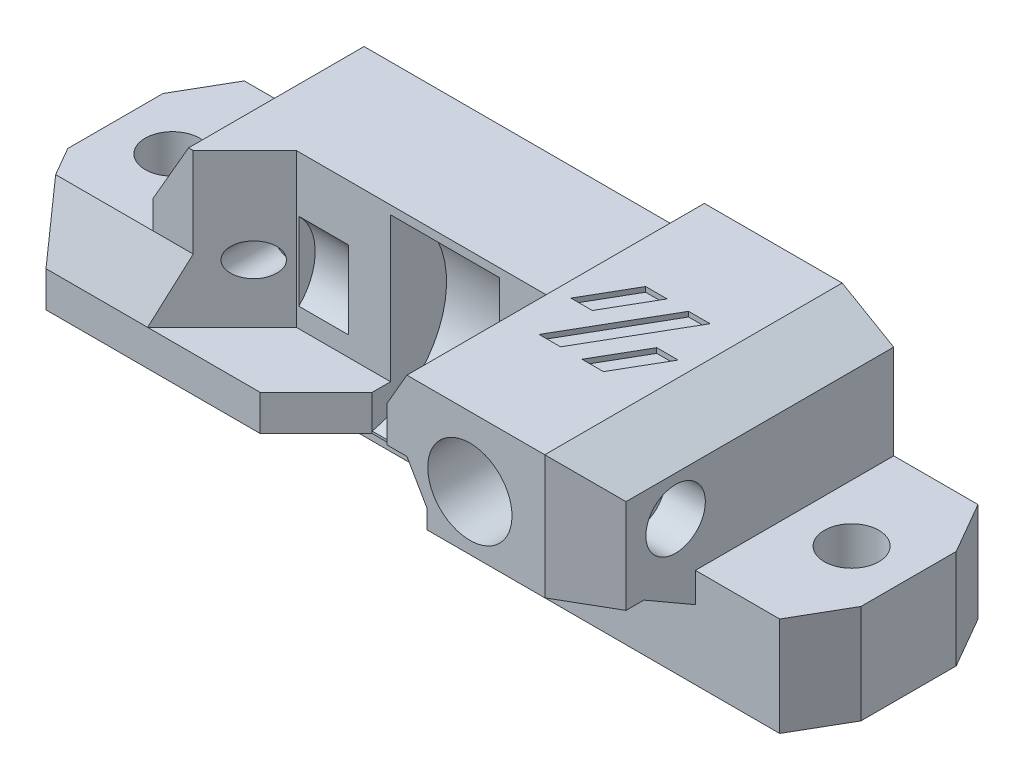
SolidWorks part; units mm, degrees
material "ABS"
ref_plane "Ebene vorne" through (0, 0, 0) normal (0, 0, 1) x (1, 0, 0)
ref_plane "Ebene oben" through (0, 0, 0) normal (0, 1, 0) x (1, 0, 0)
ref_plane "Ebene rechts" through (0, 0, 0) normal (1, 0, 0) x (0, 0, -1)
sketch "Skizze1" plane through (0, 0, 0) normal (1, 0, 0) x (0, 0, -1)
  line L0 (0, 0) -> (0, 20)
  line L1 (0, 0) -> (20, 0)
  line L2 (-19.5, -490) -> (-19.5, 10) construction
  line L3 (-19.5, 10) -> (-11.5, 10) construction
  line L4 (-11.5, 10) -> (-11.5, -490) construction
  line L5 (-11.5, -490) -> (-19.5, -490) construction
  line L6 (-15.5, 10) -> (-15.5, -490) construction
  line L7 (-9.5, -7) -> (-9.5, -10) construction
  line L8 (-22.5, 20) -> (-22.5, -10)
  line L9 (-22.5, -10) -> (20, -10)
  line L10 (20, -10) -> (20, 0)
  line L11 (0, 20) -> (-22.5, 20)
  line L12 (-23.5, -11) -> (-7.5, -11) construction
  line L13 (-7.5, -11) -> (-5.5, -16.495) construction
  line L14 (-5.5, -16.495) -> (-5.5, -78.505) construction
  line L15 (-5.5, -78.505) -> (-7.5, -84) construction
  line L16 (-7.5, -84) -> (-23.5, -84) construction
  line L17 (-23.5, -84) -> (-25.5, -78.505) construction
  line L18 (-25.5, -78.505) -> (-25.5, -16.495) construction
  line L19 (-25.5, -16.495) -> (-23.5, -11) construction
  line L20 (-2, 2.5) -> (-2, -84) construction
  circle A0 centre (-9.5, 2.5) radius 6.5 construction
  circle A1 centre (-9.5, 2.5) radius 7.5 construction
  circle A2 centre (-9.5, 2.5) radius 9.5 construction
  point P14 (-16, 2.5)
  point P15 (-9.5, -7)
  point P29 (-15.5, -11)
  point P30 (-2, 2.5)
  dimension "D2" = 15
  dimension "D3" = 13
  dimension "D5" = 19
  dimension "D1" = 20
  dimension "D4" = 15.5
  dimension "D6" = 500
  dimension "D7" = 10
  dimension "D8" = 8
  dimension "D9" = 0.5
  dimension "D10" = 3
  dimension "D11" = 10
  dimension "D12" = 17.5
  dimension "D13" = 3
  dimension "D14" = 73
  dimension "D15" = 70
  dimension "D16" = 70
  dimension "D17" = 2
  dimension "D18" = 20
  dimension "D19" = 1
  dimension "D20" = 3.5
extrude "Aufsatz-Linear austragen1" add sketch "Skizze1" along normal blind 80
sketch "Skizze2" plane through (0, 20, 0) normal (0, 1, 0) x (1, 0, 0)
  line L0 (80, 0) -> (80, -22.5) construction
  line L1 (80, 0) -> (0, 0) construction
  circle A0 centre (55.75, -15.5) radius 4.25
  point P2 (60, -15.5)
  dimension "D1" = 8.5
  dimension "D2" = 20
  dimension "D3" = 15.5
extrude "Schnitt-Linear austragen1" cut sketch "Skizze2" against normal up to surface (30 mm away) up to face at (40, -10, 1.25)
sketch "Skizze3" plane through (0, -10, 0) normal (0, -1, 0) x (1, 0, 0)
  line L0 (48.4, 9.5) -> (18.6, 9.5) construction
  line L1 (32.75, 16) -> (38.75, 16) construction
  line L2 (32.75, 16) -> (32.75, 3) construction
  line L3 (32.75, 3) -> (38.75, 3) construction
  line L4 (38.75, 16) -> (38.75, 3) construction
  line L5 (35.75, 16) -> (35.75, 3) construction
  line L6 (80, 0) -> (0, 0) construction
  line L7 (45.75, 12) -> (25.75, 12) construction
  line L8 (45.75, 12) -> (45.75, 7) construction
  line L9 (45.75, 7) -> (25.75, 7) construction
  line L10 (25.75, 12) -> (25.75, 7) construction
  line L11 (25.75, 14.25) -> (21.25, 14.25) construction
  line L12 (25.75, 14.25) -> (25.75, 4.75) construction
  line L13 (25.75, 4.75) -> (21.25, 4.75) construction
  line L14 (21.25, 14.25) -> (21.25, 4.75) construction
  line L15 (31.75, 17) -> (32.75, 17) construction
  line L16 (31.75, 17) -> (31.75, 2) construction
  line L17 (31.75, 2) -> (32.75, 2) construction
  line L18 (32.75, 17) -> (32.75, 2) construction
  line L19 (39.75, 17) -> (38.75, 17) construction
  line L20 (39.75, 17) -> (39.75, 2) construction
  line L21 (39.75, 2) -> (38.75, 2) construction
  line L22 (38.75, 17) -> (38.75, 2) construction
  line L23 (80, 0) -> (0, 0) construction
  line L24 (49.1736, 15) -> (17.8264, 15) construction
  line L25 (17.8264, 4) -> (49.1736, 4) construction
  line L26 (49.1736, 15) -> (51.05, 11.75) construction
  line L27 (51.05, 11.75) -> (51.05, 7.25) construction
  line L28 (51.05, 7.25) -> (49.1736, 4) construction
  line L29 (33.5, 15) -> (33.5, 4) construction
  line L30 (15.95, 7.25) -> (17.8264, 4) construction
  line L31 (15.95, 11.75) -> (15.95, 7.25) construction
  line L32 (17.8264, 15) -> (15.95, 11.75) construction
  line L33 (49.3991, 22.5) -> (47.4046, 19.0453)
  line L34 (80, 22.5) -> (0, 22.5) construction
  line L35 (47.4046, 19.0453) -> (47.4046, 15.4)
  line L36 (47.4046, 15.4) -> (49.4046, 15.4)
  line L37 (49.4046, 15.4) -> (51.45, 11.8572)
  line L38 (51.45, 11.8572) -> (51.45, 7.1428)
  line L39 (51.45, 7.1428) -> (49.4046, 3.6)
  line L40 (49.4046, 3.6) -> (17.5954, 3.6)
  line L41 (47.4046, 15.4) -> (47.4046, 15) construction
  line L42 (49.1736, 15) -> (49.52, 15.2) construction
  line L43 (51.05, 11.75) -> (51.45, 11.75) construction
  line L44 (51.05, 7.25) -> (51.3964, 7.05) construction
  line L45 (15.55, 11.8572) -> (17.5954, 15.4)
  line L46 (0, 22.5) -> (0, -20) construction
  line L47 (15.55, 11.8572) -> (15.55, 7.1428)
  line L48 (15.55, 7.1428) -> (17.5954, 3.6)
  line L49 (15.95, 11.75) -> (15.55, 11.75) construction
  line L50 (15.95, 7.25) -> (15.6036, 7.05) construction
  line L51 (17.8264, 4) -> (17.8264, 3.6) construction
  line L52 (17.8264, 0) -> (0, 0) construction
  line L53 (0, 0) -> (0, 19.0453) construction
  line L54 (17.5954, 15.4) -> (19.5954, 15.4)
  line L55 (19.5954, 19.0453) -> (0, 19.0453)
  line L56 (17.8264, 15) -> (17.48, 15.2) construction
  line L57 (17.8264, 15) -> (17.8264, 15.4) construction
  line L58 (19.5954, 15.4) -> (19.5954, 19.0453)
  line L59 (0, 19.0453) -> (0, 22.5)
  line L60 (0, 22.5) -> (49.3991, 22.5)
  line L63 (39.75, 14.25) -> (40.75, 14.25) construction
  line L64 (39.75, 14.25) -> (39.75, 4.75) construction
  line L65 (39.75, 4.75) -> (40.75, 4.75) construction
  line L66 (40.75, 14.25) -> (40.75, 4.75) construction
  line L67 (31.75, 14.25) -> (30.75, 14.25) construction
  line L68 (31.75, 14.25) -> (31.75, 4.75) construction
  line L69 (31.75, 4.75) -> (30.75, 4.75) construction
  line L70 (30.75, 14.25) -> (30.75, 4.75) construction
  circle A0 centre (48.4, 9.5) radius 1.65
  circle A1 centre (18.6, 9.5) radius 1.65
  circle A2 centre (55.75, 15.5) radius 4.25 construction
  circle A3 centre (55.75, 15.5) radius 4.25 construction
  point P8 (32.75, 9.5)
  point P11 (35.75, 9.5)
  point P22 (21.25, 9.5)
  point P23 (45.75, 9.5)
  point P26 (51.5, 15.5)
  point P27 (50.05, 9.5)
  point P28 (46.75, 9.5)
  point P37 (20.25, 9.5)
  point P44 (51.05, 9.5)
  point P51 (16.95, 9.5)
  point P91 (40.75, 9.5)
  dimension "D1" = 3.3
  dimension "D4" = 20
  dimension "D3" = 6
  dimension "D5" = 20
  dimension "D6" = 4.5
  dimension "D7" = 9.5
  dimension "D8" = 5
  dimension "D9" = 1
  dimension "D10" = 1.45
  dimension "D11" = 13
  dimension "D12" = 8
  dimension "D13" = 5
  dimension "D14" = 1
  dimension "D15" = 29.8
  dimension "D16" = 0.5
  dimension "D17" = 15
  dimension "D18" = 1
  dimension "D19" = 1
  dimension "D20" = 1
  dimension "D21" = 60
  dimension "D22" = 4.5
  dimension "D23" = 1
  dimension "D24" = 0.4
  dimension "D25" = 9
  dimension "D26" = 2
  dimension "D27" = 10
  dimension "D28" = 9.5
  dimension "D29" = 5
extrude "Schnitt-Linear austragen2" cut sketch "Skizze3" against normal offset from surface (17.5 mm away) 12.5 up to face at (55.75, 20, 19.75)
sketch "Skizze4" plane through (0, -10, 0) normal (0, -1, 0) x (1, 0, 0)
  circle A1 centre (18.6, 9.5) radius 1.65
  circle A2 centre (18.6, 9.5) radius 1.65
  circle A3 centre (48.4, 9.5) radius 1.65
  circle A4 centre (48.4, 9.5) radius 1.65
  dimension "D1" = 0
  dimension "D2" = 0
extrude "Schnitt-Linear austragen3" cut sketch "Skizze4" against normal up to surface (30 mm away) up to face at (55.75, 20, 19.75)
sketch "Skizze5" plane through (0, 0, 0) normal (0, 0, -1) x (-1, 0, 0)
  line L0 (-80, 0) -> (0, 0) construction
  line L1 (-80, 0) -> (-80, 20) construction
  line L2 (-5.75, 10) -> (0, 10) construction
  line L3 (0, 0) -> (0, 20) construction
  line L4 (-74.25, 10) -> (-80, 10) construction
  circle A0 centre (-5.75, 10) radius 2.75
  circle A1 centre (-74.25, 10) radius 2.75
  point P8 (-77, 10)
  point P13 (-3, 10)
  dimension "D2" = 5.5
  dimension "D1" = 10
  dimension "D3" = 3
extrude "Schnitt-Linear austragen4" cut sketch "Skizze5" against normal up to surface (22.5 mm away) up to face at (43.133, 5.8333, 22.5)
sketch "Skizze6" plane through (0, 0, 0) normal (0, 1, 0) x (1, 0, 0)
  line L0 (0, 10) -> (80, 10) construction
  line L2 (0, 20) -> (0, 0) construction
  line L3 (80, 20) -> (80, 0) construction
  line L4 (80, 0) -> (0, 0) construction
  circle A0 centre (40, 10) radius 2.75
  dimension "D2" = 5.5
  dimension "D1" = 10
extrude "Schnitt-Linear austragen5" cut sketch "Skizze6" against normal up to surface (10 mm away) up to face at (55.75, -10, 19.75)
sketch "Skizze7" plane through (0, 20, 0) normal (0, 1, 0) x (1, 0, 0)
  line L1 (21.8909, -9.5) -> (20.2454, -6.65)
  line L2 (20.2454, -6.65) -> (16.9546, -6.65)
  line L3 (16.9546, -6.65) -> (15.3091, -9.5)
  line L4 (15.3091, -9.5) -> (16.9546, -12.35)
  line L5 (16.9546, -12.35) -> (20.2454, -12.35)
  line L6 (20.2454, -12.35) -> (21.8909, -9.5)
  line L7 (51.6909, -9.5) -> (50.0454, -6.65)
  line L8 (50.0454, -6.65) -> (46.7546, -6.65)
  line L9 (46.7546, -6.65) -> (45.1091, -9.5)
  line L10 (45.1091, -9.5) -> (46.7546, -12.35)
  line L11 (46.7546, -12.35) -> (50.0454, -12.35)
  line L12 (50.0454, -12.35) -> (51.6909, -9.5)
  circle A0 centre (18.6, -9.5) radius 2.85 construction
  circle A1 centre (48.4, -9.5) radius 2.85 construction
  dimension "D1" = 5.7
extrude "Schnitt-Linear austragen6" cut sketch "Skizze7" against normal offset from surface (9.5 mm away) 3 up to face at (31.0127, 7.5, 13.9291)
sketch "Skizze8" plane through (0, 7.5, 0) normal (0, -1, 0) x (1, 0, 0)
  line L0 (49.3991, 22.5) -> (47.4046, 19.0453) construction
  line L2 (49.3991, 22.5) -> (47.4046, 19.0453)
  line L3 (0, 22.5) -> (0, 10)
  line L4 (0, 22.5) -> (49.3991, 22.5)
  line L5 (47.4046, 19.0453) -> (15.0812, 19.0453)
  line L6 (80, 22.5) -> (68.5, 22.5)
  line L7 (80, 22.5) -> (80, 10)
  line L8 (80, 10) -> (68.5, 10)
  line L9 (80, 0) -> (80, 22.5) construction
  line L10 (80, 22.5) -> (0, 22.5) construction
  line L12 (68.5, 22.5) -> (68.5, 10)
  line L13 (55.75, 15.5) -> (47.9558, 20) construction
  line L15 (71.5, 0) -> (77, 0) construction
  line L16 (71.5, 0) -> (77, 0) construction
  line L17 (19.5954, 19.0453) -> (6.8956, 19.0453) construction
  line L18 (0, 10) -> (11.5, 10)
  line L19 (11.5, 10) -> (11.5, 12.8424)
  line L20 (11.5, 12.8424) -> (15.0812, 19.0453)
  line L21 (3, 0) -> (8.5, 0) construction
  line L22 (3, 0) -> (8.5, 0) construction
  line L24 (15.55, 11.8572) -> (17.5954, 15.4) construction
  circle A0 centre (55.75, 15.5) radius 4.25 construction
  circle A1 centre (55.75, 15.5) radius 4.25 construction
  point P15 (60, 15.5)
  dimension "D2" = 10
  dimension "D3" = 3
  dimension "D4" = 3
  dimension "D5" = 4
extrude "Schnitt-Linear austragen7" cut sketch "Skizze8" against normal up to surface and the other way up to surface up to face at (48.4, 20, 9.5) other way up to face at (40, -10, -7.25)
sketch "Skizze9" plane through (51.45, 0, 0) normal (-1, 0, 0) x (0, 0, 1)
  line L0 (9.5, 7.5) -> (9.5, -10) construction
  line L1 (11.8572, 7.5) -> (7.1428, 7.5) construction
  line L2 (7.1428, -10) -> (11.8572, -10) construction
  line L3 (0, 3.65) -> (0, -10)
  line L4 (0, -10) -> (19, -10)
  line L5 (19, -10) -> (19, 3.65)
  circle A0 centre (9.5, 3.65) radius 6.5 construction
  circle A1 centre (9.5, 3.65) radius 9.5 construction
  arc A2 (19, 3.65) -> (0, 3.65) centre (9.5, 3.65) ccw
  line M1 (11.8572, 7.5) -> (7.1428, 7.5)
  line M2 (7.1428, 7.5) -> (7.1428, -10)
  line M3 (7.1428, -10) -> (11.8572, -10)
  line M4 (11.8572, -10) -> (11.8572, 7.5)
  dimension "D1" = 13
  dimension "D2" = 19
  dimension "D3" = 3.85
extrude "Schnitt-Linear austragen8" cut sketch "Skizze9" along normal blind 11 from offset 10.2 contours L5 A2 L3 L4 M2 M1 M4 | M4 M1 M2 M3
sketch "Skizze10" plane through (51.45, 0, 0) normal (-1, 0, 0) x (0, 0, 1)
  line L0 (9.5, 7.5) -> (9.5, 3.65) construction
  line L1 (11.8572, 7.5) -> (7.1428, 7.5) construction
  circle A0 centre (9.5, 3.65) radius 5.5
  dimension "D1" = 11
  dimension "D2" = 3.85
extrude "Schnitt-Linear austragen9" cut sketch "Skizze10" along normal blind 5 from offset 25.45
sketch "Skizze11" plane through (0, 0, 0) normal (0, 0, -1) x (-1, 0, 0)
  line L0 (-20.75, 7.5) -> (-15.55, 2.3)
  line L1 (-46.25, 7.5) -> (-51.45, 7.5)
  line L4 (-15.55, 2.3) -> (-15.55, 7.5)
  line L6 (-15.55, 7.5) -> (-20.75, 7.5)
  line L8 (-15.55, 7.5) -> (-15.55, -10) construction
  line L9 (-16.95, 10.5) -> (-20.25, 10.5) construction
  line L10 (-16.95, 10.5) -> (-20.25, 10.5) construction
  line L11 (-46.75, 10.5) -> (-50.05, 10.5) construction
  line L12 (-16.95, 10.5) -> (-20.25, 10.5)
  line L13 (-46.75, 10.5) -> (-50.05, 10.5) construction
  line L14 (-18.6, 10.5) -> (-18.6, 7.5) construction
  line L15 (-48.4, 10.5) -> (-48.4, 7.5) construction
  line L16 (-51.45, 7.5) -> (-51.45, 2.3)
  line L17 (-51.45, 2.3) -> (-46.25, 7.5)
  line L21 (-51.45, 7.5) -> (-51.45, -10) construction
  line L22 (-19.5954, 7.5) -> (-47.4046, 7.5) construction
  dimension "D2" = 2.15
  dimension "D3" = 45
extrude "Aufsatz-Linear austragen2" add sketch "Skizze11" against normal up to surface (19.0453 mm away)
sketch "Skizze12" plane through (0, 10.5, 0) normal (0, 1, 0) x (1, 0, 0)
  circle A0 centre (18.6, -9.5) radius 1.65 construction
  circle A1 centre (48.4, -9.5) radius 1.65 construction
  circle A2 centre (18.6, -9.5) radius 1.65
  circle A3 centre (48.4, -9.5) radius 1.65
extrude "Schnitt-Linear austragen10" cut sketch "Skizze12" against normal up to surface (20.5 mm away) up to face at (40, -10, -7.25)
chamfer "Fase1" distance 1.6 angle 45 2 edges at (48.4, 10.5, 7.85) (18.6, 10.5, 7.85)
sketch "Skizze15" plane through (80, 0, 0) normal (1, 0, 0) x (0, 0, -1)
  line L1 (0, 0) -> (20, 0)
  line L2 (0, 0) -> (0, -10)
  line L3 (0, -10) -> (20, -10)
  line L4 (20, 0) -> (20, -10)
extrude "Schnitt-Linear austragen12" cut sketch "Skizze15" against normal up to surface (80 mm away) up to face at (0, 3.3333, -3.3333)
sketch "Skizze16" plane through (0, 0, 19.0453) normal (0, 0, 1) x (1, 0, 0)
  line L0 (0, -10) -> (0, 2.3)
  line L1 (0, 2.3) -> (15.55, 2.3)
  line L2 (15.55, 2.3) -> (19.5954, 6.3454)
  line L3 (19.5954, 6.3454) -> (19.5954, -10)
  line L4 (19.5954, -10) -> (0, -10)
  line L5 (0, 20) -> (0, -10) construction
  line L6 (11.5, -10) -> (0, -10) construction
extrude "Schnitt-Linear austragen13" cut sketch "Skizze16" against normal up to surface (15.4453 mm away) up to face at (45.5118, -0.1309, 3.6)
sketch "Skizze17" plane through (0, 0, 3.6) normal (0, 0, 1) x (1, 0, 0)
  line L0 (0, 2.3) -> (0, -10) construction
  line L1 (49.4046, -10) -> (0, -10)
  line L2 (49.4046, -10) -> (49.4046, 0)
  line L3 (49.4046, 0) -> (0, 0)
  line L4 (0, -10) -> (0, 0)
  line L5 (11.5, 20) -> (0, 20) construction
  dimension "D1" = 20
extrude "Schnitt-Linear austragen14" cut sketch "Skizze17" against normal up to surface (3.6 mm away) up to face at (71.5, 10, 0)
sketch "Skizze20" plane through (0, 0, 0) normal (-1, 0, 0) x (0, 0, 1)
  line L0 (10, 2.3) -> (3.6, 2.3)
  line L1 (3.6, 2.3) -> (3.6, 0)
  line L2 (3.6, 0) -> (10, 2.3)
extrude "Aufsatz-Linear austragen3" add sketch "Skizze20" against normal up to surface (15.55 mm away) up to face at (20.25, 7, 9.5)
sketch "Skizze21" plane through (80, 0, 0) normal (1, 0, 0) x (0, 0, -1)
  line L0 (0, -10) -> (0, 0)
  line L1 (0, -10) -> (0, 20) construction
  line L2 (0, 0) -> (-10, 0)
  line L3 (-10, 20) -> (-10, -10) construction
  line L4 (-10, 0) -> (-10, -10)
  line L5 (-10, -10) -> (0, -10)
  line L6 (-10, -10) -> (0, -10) construction
  line L7 (-19.75, -10) -> (-11.25, -10) construction
  line L8 (-19.75, -10) -> (-11.25, -10) construction
  dimension "D1" = 1.25
extrude "Schnitt-Linear austragen18" cut sketch "Skizze21" against normal up to surface (30.5954 mm away) up to face at (49.4046, -5, 1.8)
sketch "Skizze22" plane through (68.5, 0, 0) normal (1, 0, 0) x (0, 0, -1)
  line L0 (-19.75, -10) -> (-11.25, -10) construction
  line L1 (-19.75, -10) -> (-11.25, -10) construction
  line L2 (-15.5, -10) -> (-15.5, 20) construction
  line L3 (-10, 20) -> (-22.5, 20) construction
  circle A0 centre (-15.5, -2) radius 2.25
  dimension "D1" = 4.5
  dimension "D2" = 8
extrude "Schnitt-Linear austragen19" cut sketch "Skizze22" against normal up to surface (9.1444 mm away) up to face at (55.75, -10, 19.75)
sketch "Skizze23" plane through (68.5, 0, 0) normal (1, 0, 0) x (0, 0, -1)
  circle A0 centre (-15.5, -2) radius 3
  dimension "D1" = 6
extrude "Schnitt-Linear austragen20" cut sketch "Skizze23" against normal blind 4
chamfer "Fase2" distance 3 angle 60 1 edges at (68.5, 5, 22.5) first distance on face at (68.5, -2, 12.5)
sketch "Skizze24" plane through (80, 0, 0) normal (1, 0, 0) x (0, 0, -1)
  line L0 (0, 0) -> (0, 20) construction
  line L1 (0, 13) -> (2, 13) construction
  line L2 (0, 13) -> (0, 7)
  line L3 (0, 7) -> (2, 7)
  line L4 (2, 13) -> (2, 7)
  line L5 (0, 13) -> (2, 11)
  point P6 (0, 10)
  line M2 (0, 0) -> (0, 20)
  dimension "D1" = 6
  dimension "D2" = 2
  dimension "D3" = 45
extrude "Aufsatz-Linear austragen4" add sketch "Skizze24" against normal offset from surface (46 mm away) 17 from offset 17 contours L5 L3 L4 M2 up to face at (0, 8.46, 4.72)
chamfer "Fase3" distance 3 angle 60 7 edges at (80, 20, 5) (68.5, -10, 14.75) (0, 0, 1.8) (0, 1.15, 6.8) (80, 0, 5) (65.9019, -10, 21) (0, 20, 5)
chamfer "Fase4" distance 3 angle 60 1 edges at (59.975, 0, 10) first distance on face at (57.1631, 0, 5.5429)
sketch "Skizze27" plane through (0, 0, 22.5) normal (0, 0, 1) x (1, 0, 0)
  line L0 (58.0288, 9.7801) -> (60.1938, 9.7801)
  line L1 (60.1938, 9.7801) -> (54.6742, 0.2199)
  line L2 (54.6742, 0.2199) -> (52.5092, 0.2199)
  line L3 (52.5092, 0.2199) -> (58.0288, 9.7801)
  line L4 (53.6986, 9.7801) -> (55.8637, 9.7801)
  line L5 (55.8637, 9.7801) -> (53.1039, 5)
  line L6 (53.1039, 5) -> (50.9388, 5)
  line L7 (50.9388, 5) -> (53.6986, 9.7801)
  line L8 (59.5991, 5) -> (56.8393, 0.2199)
  line L9 (56.8393, 0.2199) -> (59.0043, 0.2199)
  line L10 (59.0043, 0.2199) -> (61.7642, 5)
  line L11 (61.7642, 5) -> (59.5991, 5)
  line L12 (60.1015, 11.4952) -> (52.6015, -1.4952) construction
  line L13 (63.8515, 9.3301) -> (56.3515, 13.6603) construction
  line L14 (56.3515, 13.6603) -> (48.8515, 9.3301) construction
  line L15 (48.8515, 9.3301) -> (48.8515, 0.6699) construction
  line L16 (48.8515, 0.6699) -> (56.3515, -3.6603) construction
  line L17 (56.3515, -3.6603) -> (63.8515, 0.6699) construction
  line L18 (63.8515, 0.6699) -> (63.8515, 9.3301) construction
  line L19 (59.5991, 5) -> (57.434, 5) construction
  line L20 (53.1039, 5) -> (55.269, 5) construction
  line L21 (63.3038, 20) -> (49.3991, 20) construction
  line L22 (48.8515, 5) -> (56.3515, 5) construction
  line L23 (59.0043, 0.2199) -> (59.0043, 0.6699) construction
  line L24 (60.1938, 9.7801) -> (60.1938, 9.3301) construction
  circle A0 centre (56.3515, 5) radius 7.5 construction
  point P22 (59.1113, 9.7801)
  point P25 (56.3515, 20)
  dimension "D1" = 15
  dimension "D2" = 1.875
  dimension "D3" = 0.45
  dimension "D4" = 15
extrude "Schnitt-Linear austragen22" cut sketch "Skizze27" against normal blind 0.5
sketch "Skizze28" plane through (0, 0, 0) normal (0, 0, -1) x (-1, 0, 0)
  line L0 (-30.25, 5.65) -> (-24.6, 0)
  line L1 (-3, 0) -> (-30.25, 0) construction
  line L2 (-24.6, 0) -> (-46.9, 0)
  line L3 (-41.25, 0) -> (-77, 0) construction
  line L4 (-46.9, 0) -> (-41.25, 5.65)
  line L5 (-41.25, 5.65) -> (-30.25, 5.65)
  line L8 (-41.25, 3.65) -> (-41.25, 0) construction
  line L9 (-30.25, 3.65) -> (-30.25, 0) construction
  line L10 (-30.25, 3.65) -> (-41.25, 3.65) construction
  dimension "D1" = 45
  dimension "D2" = 45
  dimension "D3" = 2
extrude "Schnitt-Linear austragen23" cut sketch "Skizze28" against normal up to surface (3.6 mm away) up to face at (45.5118, 3.8691, 3.6)
move or copy body "Körper-Verschieben/Kopieren1" bodies to move or copy 125 copy no rotation origin (0, 5, 10) rotation axis (-1, 0, 0) rotation angle 90
